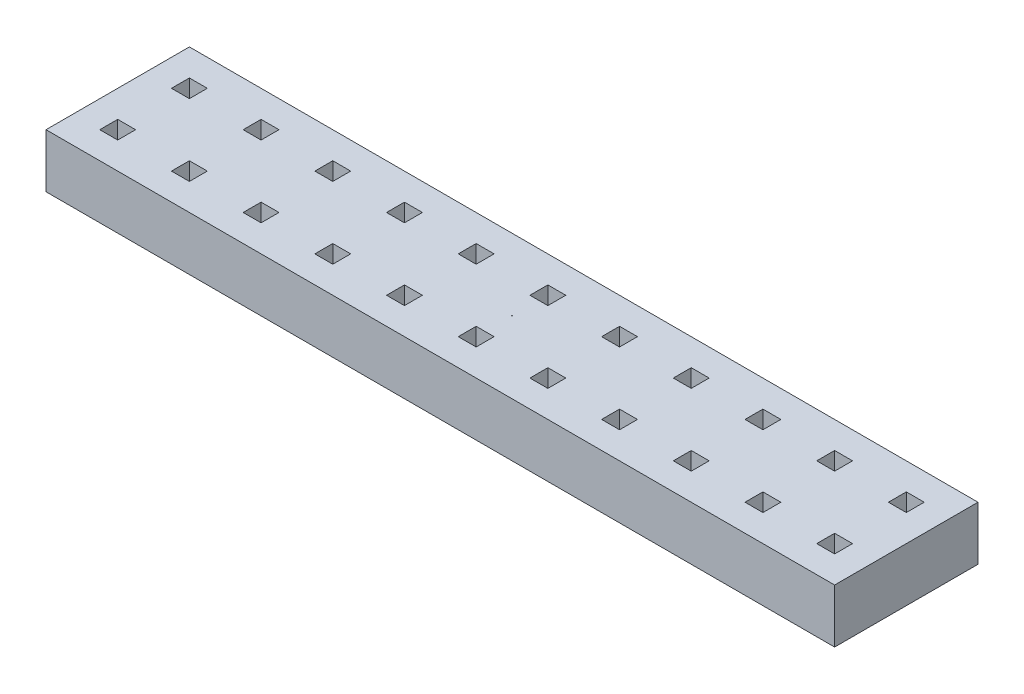
SolidWorks part; units mm, degrees
ref_plane "Front Plane" through (0, 0, 0) normal (0, 0, 1) x (1, 0, 0)
ref_plane "Top Plane" through (0, 0, 0) normal (0, 1, 0) x (1, 0, 0)
ref_plane "Right Plane" through (0, 0, 0) normal (1, 0, 0) x (0, 0, -1)
sketch "Sketch1" plane through (0, 0, 0) normal (0, 1, 0) x (1, 0, 0)
  line L1 (0, 0) -> (22, 0)
  line L2 (0, 0) -> (0, 4)
  line L3 (0, 4) -> (22, 4)
  line L4 (22, 0) -> (22, 4)
extrude "Boss-Extrude1" add sketch "Sketch1" along normal blind 1.5
sketch "Sketch2" plane through (0, 1.5, 0) normal (0, 1, 0) x (1, 0, 0)
  line L0 (2.75, 3.25) -> (2.75, 2.75)
  line L1 (0.75, 3.25) -> (1.25, 3.25)
  line L2 (0.75, 3.25) -> (0.75, 2.75)
  line L3 (0.75, 2.75) -> (1.25, 2.75)
  line L4 (1.25, 3.25) -> (1.25, 2.75)
  line L5 (2.75, 3.25) -> (3.25, 3.25)
  line L6 (3.25, 3.25) -> (3.25, 2.75)
  line L7 (2.75, 2.75) -> (3.25, 2.75)
  line L8 (4.75, 3.25) -> (4.75, 2.75)
  line L9 (4.75, 3.25) -> (5.25, 3.25)
  line L10 (5.25, 3.25) -> (5.25, 2.75)
  line L11 (4.75, 2.75) -> (5.25, 2.75)
  line L12 (6.75, 3.25) -> (6.75, 2.75)
  line L13 (6.75, 3.25) -> (7.25, 3.25)
  line L14 (7.25, 3.25) -> (7.25, 2.75)
  line L15 (6.75, 2.75) -> (7.25, 2.75)
  line L16 (8.75, 3.25) -> (8.75, 2.75)
  line L17 (8.75, 3.25) -> (9.25, 3.25)
  line L18 (9.25, 3.25) -> (9.25, 2.75)
  line L19 (8.75, 2.75) -> (9.25, 2.75)
  line L20 (10.75, 3.25) -> (10.75, 2.75)
  line L21 (10.75, 3.25) -> (11.25, 3.25)
  line L22 (11.25, 3.25) -> (11.25, 2.75)
  line L23 (10.75, 2.75) -> (11.25, 2.75)
  line L24 (12.75, 3.25) -> (12.75, 2.75)
  line L25 (12.75, 3.25) -> (13.25, 3.25)
  line L26 (13.25, 3.25) -> (13.25, 2.75)
  line L27 (12.75, 2.75) -> (13.25, 2.75)
  line L28 (14.75, 3.25) -> (14.75, 2.75)
  line L29 (14.75, 3.25) -> (15.25, 3.25)
  line L30 (15.25, 3.25) -> (15.25, 2.75)
  line L31 (14.75, 2.75) -> (15.25, 2.75)
  line L32 (16.75, 3.25) -> (16.75, 2.75)
  line L33 (16.75, 3.25) -> (17.25, 3.25)
  line L34 (17.25, 3.25) -> (17.25, 2.75)
  line L35 (16.75, 2.75) -> (17.25, 2.75)
  line L36 (18.75, 3.25) -> (18.75, 2.75)
  line L37 (18.75, 3.25) -> (19.25, 3.25)
  line L38 (19.25, 3.25) -> (19.25, 2.75)
  line L39 (18.75, 2.75) -> (19.25, 2.75)
  line L40 (20.75, 3.25) -> (20.75, 2.75)
  line L41 (20.75, 3.25) -> (21.25, 3.25)
  line L42 (21.25, 3.25) -> (21.25, 2.75)
  line L43 (20.75, 2.75) -> (21.25, 2.75)
  line L72 (0.75, 1.25) -> (0.75, 0.75)
  line L73 (0.75, 1.25) -> (1.25, 1.25)
  line L74 (1.25, 1.25) -> (1.25, 0.75)
  line L75 (0.75, 0.75) -> (1.25, 0.75)
  line L76 (2.75, 1.25) -> (2.75, 0.75)
  line L77 (2.75, 1.25) -> (3.25, 1.25)
  line L78 (3.25, 1.25) -> (3.25, 0.75)
  line L79 (2.75, 0.75) -> (3.25, 0.75)
  line L80 (4.75, 1.25) -> (4.75, 0.75)
  line L81 (4.75, 1.25) -> (5.25, 1.25)
  line L82 (5.25, 1.25) -> (5.25, 0.75)
  line L83 (4.75, 0.75) -> (5.25, 0.75)
  line L84 (6.75, 1.25) -> (6.75, 0.75)
  line L85 (6.75, 1.25) -> (7.25, 1.25)
  line L86 (7.25, 1.25) -> (7.25, 0.75)
  line L87 (6.75, 0.75) -> (7.25, 0.75)
  line L88 (8.75, 1.25) -> (8.75, 0.75)
  line L89 (8.75, 1.25) -> (9.25, 1.25)
  line L90 (9.25, 1.25) -> (9.25, 0.75)
  line L91 (8.75, 0.75) -> (9.25, 0.75)
  line L92 (10.75, 1.25) -> (10.75, 0.75)
  line L93 (10.75, 1.25) -> (11.25, 1.25)
  line L94 (11.25, 1.25) -> (11.25, 0.75)
  line L95 (10.75, 0.75) -> (11.25, 0.75)
  line L96 (12.75, 1.25) -> (12.75, 0.75)
  line L97 (12.75, 1.25) -> (13.25, 1.25)
  line L98 (13.25, 1.25) -> (13.25, 0.75)
  line L99 (12.75, 0.75) -> (13.25, 0.75)
  line L100 (14.75, 1.25) -> (14.75, 0.75)
  line L101 (14.75, 1.25) -> (15.25, 1.25)
  line L102 (15.25, 1.25) -> (15.25, 0.75)
  line L103 (14.75, 0.75) -> (15.25, 0.75)
  line L104 (16.75, 1.25) -> (16.75, 0.75)
  line L105 (16.75, 1.25) -> (17.25, 1.25)
  line L106 (17.25, 1.25) -> (17.25, 0.75)
  line L107 (16.75, 0.75) -> (17.25, 0.75)
  line L108 (18.75, 1.25) -> (18.75, 0.75)
  line L109 (18.75, 1.25) -> (19.25, 1.25)
  line L110 (19.25, 1.25) -> (19.25, 0.75)
  line L111 (18.75, 0.75) -> (19.25, 0.75)
  line L112 (20.75, 1.25) -> (20.75, 0.75)
  line L113 (20.75, 1.25) -> (21.25, 1.25)
  line L114 (21.25, 1.25) -> (21.25, 0.75)
  line L115 (20.75, 0.75) -> (21.25, 0.75)
  dimension "D1" = 11
  dimension "D2" = 2
extrude "Cut-Extrude1" cut sketch "Sketch2" against normal blind 2
sketch "Sketch3" plane through (0, 1.5, 0) normal (0, 1, 0) x (1, 0, 0)
  circle A0 centre (11, 2) radius 0.01
  point P0 (11, 2)
ref_axis "Axis1" [suppressed] through (11, -5.3844, -2) along (0, 1, 0)
extrude "Cut-Extrude2" cut sketch "Sketch3" against normal blind 1.5
